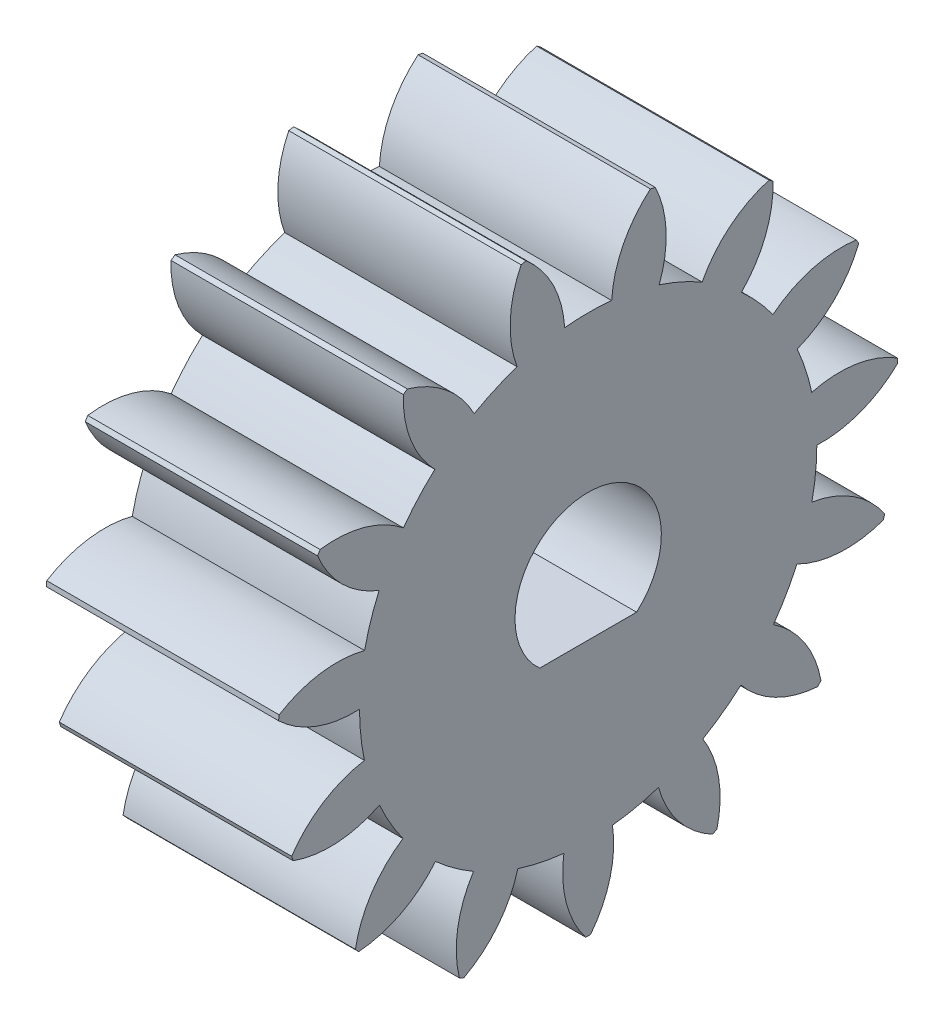
SolidWorks part; units mm, degrees
ref_plane "Plane1" through (0, 0, 0) normal (0, 0, 1) x (1, 0, 0)
ref_plane "Plane2" through (0, 0, 0) normal (0, 1, 0) x (1, 0, 0)
ref_plane "Plane3" through (0, 0, 0) normal (1, 0, 0) x (0, 0, -1)
sketch "HoldingSke" plane through (0, 0, 0) normal (0, 1, 0) x (1, 0, 0)
  line L0 (0, 0) -> (0.483, -0.1294)
  line L1 (-15, 0) -> (100, 0) construction
  line L2 (0, 0) -> (-2.1039, 2.3779)
  line L3 (0, 0) -> (-11.863, 4.5341)
  line L4 (0, 0) -> (8.3417, 2.2352)
  line L5 (0, 0) -> (-23.7986, -8.8762)
  line L6 (0, 0) -> (-10.5278, -7.1032)
  line L7 (-2.1039, 2.3779) -> (3.3639, 27.1846)
  line L8 (-76.2, 54.61) -> (-73.66, 54.61)
  line L9 (-71.009, 38.7566) -> (-53.1078, 45.2721)
  line L10 (-76.2, 71.12) -> (104.1128, 71.12)
  line L11 (0, 0) -> (-12.7, 0)
  line L12 (-76.2, 101.6) -> (-75.9714, 101.6)
  line L13 (24.9733, 27.94) -> (52.9518, 28.4284)
  line L14 (24.9733, 27.94) -> (24.9746, 27.94)
  line L15 (24.9733, 27.94) -> (100.4006, 29.5858)
  line L16 (-63.627, -2) -> (-12.827, -2)
  circle A0 centre (0, 0) radius 4
  circle A1 centre (0, 0) radius 9.4987
  circle A2 centre (0, 0) radius 12.7
  circle A3 centre (0, 0) radius 4
  dimension "Num_teeth" = 15
  dimension "Pitch_radius" = 180.3128
  dimension "Width" = 12.7
  dimension "Thickness" = 12.7
sketch "BasProSke" plane through (0, 0, 0) normal (0, 1, 0) x (1, 0, 0)
  line L0 (-10, 0) -> (60, 0) construction
  line L1 (0, 0) -> (0, 17)
  line L2 (0, 0) -> (12.7, 0)
  line L3 (12.7, 0) -> (12.7, 17)
  line L4 (12.7, 17) -> (0, 17)
  dimension "Thickness" = 12.7
  dimension "Diameter" = 34
revolve "Base-Revolve" add sketch "BasProSke" angle 360 about L0
sketch "TooCutSke" plane through (0, 0, 0) normal (1, 0, 0) x (0, 0, -1)
  line L1 (0, 0) -> (0, 107) construction
  line L2 (0, 0) -> (-1.9669, 14.8705) construction
  line L3 (0, 0) -> (-6.2184, 29.2554) construction
  line L4 (-1.9669, 14.8705) -> (-3.1092, 14.6277) construction
  arc A0 (1.2856, 12.4324) -> (-1.2856, 12.4324) centre (0, 0) ccw
  arc A1 (3.4272, 16.6769) -> (-3.4272, 16.6769) centre (0, 0) ccw
  circle A2 centre (0, 0) radius 15 construction
  circle A3 centre (0, 0) radius 14.0954 construction
  arc A4 (-1.2856, 12.4324) -> (-3.4272, 16.6769) centre (-7.2748, 12.073) ccw
  arc A5 (3.4272, 16.6769) -> (1.2856, 12.4324) centre (7.2748, 12.073) ccw
extrude "ToothCut" cut sketch "TooCutSke" along normal through all
fillet "Breaks" [suppressed] radius 0.04 tangent propagation no
fillet "RootFillets" [suppressed] radius 0.5013
pattern_circular "TeethCuts" count 15 every 24 about axis through (-10, 0, 0) along (1, 0, 0) of "ToothCut", "RootFillets", "Breaks"
sketch "HubNeaOneSke" plane through (0, 0, 0) normal (-1, 0, 0) x (0, 0, 1)
  circle A0 centre (0, 0) radius 9.4987
  dimension "Diameter" = 18.9975
extrude "HubNearOne" [suppressed] add sketch "HubNeaOneSke" along normal blind 12.7022
sketch "HubNeaBotSke" plane through (0, 0, 0) normal (-1, 0, 0) x (0, 0, 1)
  circle A0 centre (0, 0) radius 9.4987
  dimension "Diameter" = 18.9975
extrude "HubNearBoth" [suppressed] add sketch "HubNeaBotSke" along normal blind 6.3511
ref_plane "FarPln" through (12.7, 0, 0) normal (1, 0, 0) x (0, 0, -1)
sketch "HubFarSke" plane through (12.7, 0, 0) normal (1, 0, 0) x (0, 0, -1)
  circle A0 centre (0, 0) radius 9.4987
  dimension "Diameter" = 18.9975
extrude "HubFar" [suppressed] add sketch "HubFarSke" along normal blind 6.3511
sketch "BorSke" plane through (0, 0, 0) normal (1, 0, 0) x (0, 0, -1)
  circle A0 centre (0, 0) radius 4
  dimension "Diameter" = 8
extrude "Bore" cut sketch "BorSke" along normal mid plane 50.8044
sketch "KeySke" plane through (0, 0, 0) normal (1, 0, 0) x (0, 0, -1)
  line L0 (-3.175, 0) -> (-3.175, 6.54)
  line L1 (-3.175, 6.54) -> (3.175, 6.54)
  line L2 (3.175, 6.54) -> (3.175, 0)
  line L3 (0, 0) -> (0, 34) construction
  line L4 (-3.175, 0) -> (3.175, 0)
  dimension "Width" = 6.35
extrude "Keyway" [suppressed] cut sketch "KeySke" along normal mid plane 50.8044
pattern_circular "Keyway2" [suppressed] count 2 every 90 about axis through (-10, 0, 0) along (1, 0, 0) reverse direction yes
sketch "Szkic1" [suppressed] plane through (0, 0, 0) normal (1, 0, 0) x (0, 0, -1)
  line L0 (4, -5.8283) -> (4, 7.2616) construction
  line L2 (-7.7998, -4.1403) -> (-7.7998, 4.4855)
  line L3 (-7.7998, -4.1403) -> (-3, -4.1403)
  line L4 (-7.7998, 4.4855) -> (-3, 4.4855)
  line L5 (-3, -4.1403) -> (-3, 4.4855)
  circle A0 centre (0, 0) radius 4 construction
  dimension "D1" = 7
extrude "Dodanie-wyciągnięcie1" [suppressed] add sketch "Szkic1" along normal blind 9
sketch "Szkic2" plane through (0, 0, 0) normal (1, 0, 0) x (0, 0, -1)
  line L1 (-2.6458, -4) -> (2.6458, -4)
  line L2 (-2.6458, -4) -> (-2.6458, -3)
  line L3 (-2.6458, -3) -> (2.6458, -3)
  line L4 (2.6458, -4) -> (2.6458, -3)
  circle A0 centre (0, 0) radius 4 construction
  dimension "D1" = 1
extrude "Dodanie-wyciągnięcie2" add sketch "Szkic2" along normal up to surface (12.7 mm away) up to face at (12.7, 0, 4)
equation "' \"Module@HoldingSke\" = 6.35"
equation "' \"Num_teeth@HoldingSke\" = 12"
equation "' \"Ap@HoldingSke\" =  20"
equation "' \"Ap@HoldingSke\" = 20"
equation "' \"Width@HoldingSke\" = 0.5 * 25.4"
equation "' \"Hub_dia@HoldingSke\"= 1 * 25.4"
equation "' \"Hub_dia@HoldingSke\" = 1 * 25.4"
equation "' \"Overall_len@HoldingSke\" = 1.0 * 25.4"
equation "' \"Bore@HoldingSke\" = 0.75 * 25.4"
equation "' \"T_dim@HoldingSke\" = 0.1 * 25.4"
equation "' \"Width@KeySke\" = 0.25 * 25.4"
equation "' \"Show_teeth@HoldingSke\" = 13"
equation "' \"Backlash@HoldingSke\" = 0.009 * 25.4"
equation "' \"Addendum_fac@HoldingSke\" = 1.0"
equation "' \"Dedendum_fac@HoldingSke\" = 1.25"
equation "' \"Dedendum_add@HoldingSke\" = 0.00005 * 25.4"
equation "' \"Clearance_fac@HoldingSke\" = 0.25"
equation "\"Pitch@HoldingSke\"= 1 / \"Module@HoldingSke\""
equation "\"Overcut_dia@TooCutSke\" = (\"Num_teeth@HoldingSke\" + 2 * \"Addendum_fac@HoldingSke\") / \"Pitch@HoldingSke\" + 0.002 * 25.4"
equation "\"Pitch_dia@TooCutSke\" = \"Num_teeth@HoldingSke\" / \"Pitch@HoldingSke\""
equation "\"Base_dia@TooCutSke\" = \"Num_teeth@HoldingSke\" / \"Pitch@HoldingSke\" * cos((\"Ap@HoldingSke\"  * 3.14159265 / 180))"
equation "\"Root_dia@TooCutSke\" = (\"Num_teeth@HoldingSke\" + 2) / \"Pitch@HoldingSke\" - 2 * (\"Addendum_fac@HoldingSke\" + \"Dedendum_fac@HoldingSke\") / \"Pitch@HoldingSke\" - \"Dedendum_add@HoldingSke\" * 2"
equation "\"Half_ang@TooCutSke\" = 180 / \"Num_teeth@HoldingSke\""
equation "\"Half_CT@TooCutSke\" = \"Num_teeth@HoldingSke\" / \"Pitch@HoldingSke\" * sin((3.14159265 / 2 / \"Num_teeth@HoldingSke\")) / 2 - 7 * \"Backlash@HoldingSke\" / 4"
equation "\"Flank_rad@TooCutSke\" = \"Num_teeth@HoldingSke\" / \"Pitch@HoldingSke\" / 5"
equation "\"Radius@RootFillets\" = \"Clearance_fac@HoldingSke\" / \"Pitch@HoldingSke\" + \"Dedendum_add@HoldingSke\""
equation "\"Break_rad@Breaks\" = 0.02 / \"Pitch@HoldingSke\""
equation "\"Thickness@HoldingSke\"= \"Width@HoldingSke\""
equation "\"OAL@HoldingSke\" = \"Thickness@HoldingSke\""
equation "\"MHD@HoldingSke\" = (\"Num_teeth@HoldingSke\" + 2) / \"Pitch@HoldingSke\" - 2 * (\"Addendum_fac@HoldingSke\" + \"Dedendum_fac@HoldingSke\")  / \"Pitch@HoldingSke\" - \"Dedendum_add@HoldingSke\" * 2"
equation "\"MBD@HoldingSke\" = (\"Num_teeth@HoldingSke\" + 2) / \"Pitch@HoldingSke\" - 2 * (\"Addendum_fac@HoldingSke\" + \"Dedendum_fac@HoldingSke\")  / \"Pitch@HoldingSke\" - \"Dedendum_add@HoldingSke\" * 2 - 0.002 * 25.4"
equation "\"MHD@HoldingSke\" = ((sgn( \"MHD@HoldingSke\" - \"Hub_dia@HoldingSke\" )-1)*( \"MHD@HoldingSke\" - \"Hub_dia@HoldingSke\" ))/-2+ \"Hub_dia@HoldingSke\""
equation "\"MBD@HoldingSke\" = ((sgn( \"MBD@HoldingSke\" - \"Bore@HoldingSke\" )-1)*( \"MBD@HoldingSke\" - \"Bore@HoldingSke\" ))/-2+ \"Bore@HoldingSke\""
equation "\"OAL@HoldingSke\" = ((sgn( \"OAL@HoldingSke\" - \"Overall_len@HoldingSke\" )+1)*( \"OAL@HoldingSke\" - \"Overall_len@HoldingSke\" ))/2 + \"Overall_len@HoldingSke\" + 0.000002 * 25.4"
equation "\"Num_teeth@TeethCuts\" = int( \"Show_teeth@HoldingSke\" ) + 1"
equation "\"Num_teeth@TeethCuts\" = ((sgn( \"Num_teeth@TeethCuts\" - \"Num_teeth@HoldingSke\" )-1)*( \"Num_teeth@TeethCuts\" - \"Num_teeth@HoldingSke\" ))/-2+ \"Num_teeth@HoldingSke\""
equation "\"Num_teeth@TeethCuts\"= ( ( sgn ( \"Num_teeth@TeethCuts\" - 2.0 ) + 1 ) * ( \"Num_teeth@TeethCuts\" - 2.0 ) ) / 2 + 2.0"
equation "\"Angle@TeethCuts\" = 360.0 / \"Num_teeth@HoldingSke\""
equation "\"Diameter@BasProSke\" = (\"Num_teeth@HoldingSke\" + 2 * \"Addendum_fac@HoldingSke\") / \"Pitch@HoldingSke\""
equation "\"Thickness@BasProSke\"  = \"Thickness@HoldingSke\""
equation "' \"Fillet_rad@BasProSke\" =  \"Thickness@HoldingSke\" * 0.05"
equation "' \"Fillet_rad@BasProSke\" = \"Thickness@HoldingSke\" * 0.05"
equation "\"MHD@HoldingSke\" = ((sgn( \"MHD@HoldingSke\" - \"Root_dia@TooCutSke\" )-1)*( \"MHD@HoldingSke\" - \"Root_dia@TooCutSke\" ))/-2+ \"Root_dia@TooCutSke\""
equation "\"Diameter@HubNeaOneSke\" = \"MHD@HoldingSke\""
equation "\"Length@HubNearOne\" = \"OAL@HoldingSke\" - \"Thickness@BasProSke\""
equation "\"Diameter@HubNeaBotSke\" = \"MHD@HoldingSke\""
equation "\"Length@HubNearBoth\" = ( \"OAL@HoldingSke\" - \"Thickness@BasProSke\" ) / 2.0"
equation "\"Thickness@FarPln\" = \"Thickness@BasProSke\""
equation "\"Diameter@HubFarSke\" = \"MHD@HoldingSke\""
equation "\"Length@HubFar\" = ( \"OAL@HoldingSke\" - \"Thickness@BasProSke\" ) / 2.0"
equation "\"Diameter@BorSke\" = \"MBD@HoldingSke\""
equation "\"D1@Bore\" = \"OAL@HoldingSke\" * 2.0"
equation "\"D1@Keyway\" = \"OAL@HoldingSke\" * 2.0"
equation "\"Offset@KeySke\" = \"T_dim@HoldingSke\" + \"MBD@HoldingSke\" / 2.0"
